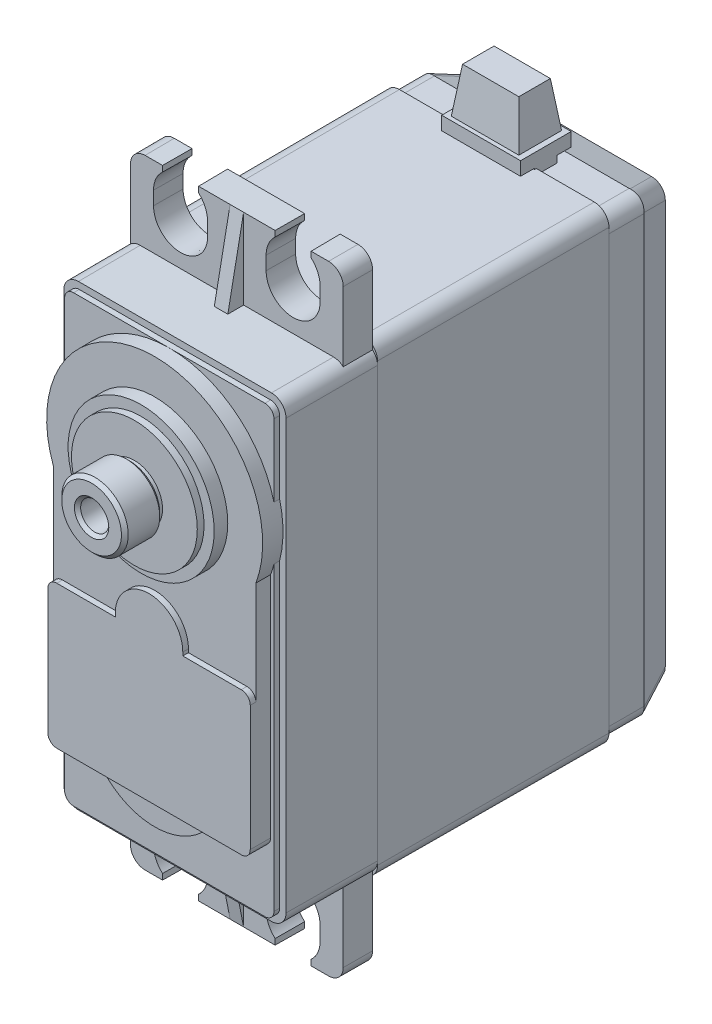
SolidWorks part; units mm, degrees
other "Camera1"
other "Camera3"
material "ABS"
ref_plane "front" through (0, 0, 0) normal (0, 0, 1) x (1, 0, 0)
ref_plane "上基準面" through (0, 0, 0) normal (0, 1, 0) x (1, 0, 0)
ref_plane "右基準面" through (0, 0, 0) normal (1, 0, 0) x (0, 0, -1)
sketch "Sketch1" plane through (0, 0, 0) normal (0, 0, 1) x (1, 0, 0)
  line L1 (-9.9, -20.7) -> (9.9, -20.7)
  line L2 (-9.9, -20.7) -> (-9.9, 20.7)
  line L3 (-9.9, 20.7) -> (9.9, 20.7)
  line L4 (9.9, -20.7) -> (9.9, 20.7)
  line L5 (-9.9, -20.7) -> (9.9, 20.7) construction
  line L6 (-9.9, 20.7) -> (9.9, -20.7) construction
  point P0 (0, 0)
  dimension "D1" = 19.8
  dimension "D2" = 41.4
extrude "Boss-Extrude1" add sketch "Sketch1" against normal blind 20.5 draft 0.15 draft outward yes
sketch "Sketch2" plane through (0, 0, -20.5) normal (0, 0, -1) x (-1, 0, 0)
  line L1 (-9.95, 20.25) -> (9.95, 20.25)
  line L2 (-9.95, 20.25) -> (-9.95, -20.25)
  line L3 (-9.95, -20.25) -> (9.95, -20.25)
  line L4 (9.95, 20.25) -> (9.95, -20.25)
  line L5 (-9.95, 20.25) -> (9.95, -20.25) construction
  line L6 (-9.95, -20.25) -> (9.95, 20.25) construction
  point P0 (0, 0)
  dimension "D1" = 19.9
  dimension "D2" = 40.5
extrude "Boss-Extrude2" add sketch "Sketch2" along normal blind 6.1
sketch "Sketch4" plane through (0, 0, 0) normal (0, 0, 1) x (1, 0, 0)
  line L0 (9.9, -20.7) -> (9.9, 20.7) construction
  line L1 (-9.9, 27.5) -> (9.9, 27.5)
  line L2 (-9.9, 27.5) -> (-9.9, -27.5)
  line L3 (-9.9, -27.5) -> (9.9, -27.5)
  line L4 (9.9, 27.5) -> (9.9, -27.5)
  line L5 (-9.9, 27.5) -> (9.9, -27.5) construction
  line L6 (-9.9, -27.5) -> (9.9, 27.5) construction
  point P0 (0, 0)
  dimension "D1" = 55
extrude "Boss-Extrude3" add sketch "Sketch4" along normal blind 2.6 draft 0.2
sketch "Sketch6" plane through (0, 0, 2.6) normal (0, 0, 1) x (1, 0, 0)
  line L0 (9.8909, -27.4909) -> (9.8909, 27.4909) construction
  line L1 (-9.8909, -20.35) -> (9.8909, -20.35)
  line L2 (-9.8909, -20.35) -> (-9.8909, 20.35)
  line L3 (-9.8909, 20.35) -> (9.8909, 20.35)
  line L4 (9.8909, -20.35) -> (9.8909, 20.35)
  line L5 (-9.8909, -20.35) -> (9.8909, 20.35) construction
  line L6 (-9.8909, 20.35) -> (9.8909, -20.35) construction
  point P0 (0, 0)
  dimension "D1" = 40.7
extrude "Boss-Extrude4" add sketch "Sketch6" along normal blind 6 draft 0.2
sketch "Sketch19" plane through (0, 0, 2.6) normal (0, 0, 1) x (1, 0, 0)
  line L0 (9.8909, 20.35) -> (-9.8909, 20.35) construction
  line L1 (-9.45, 20.35) -> (-11.45, 20.35)
  line L2 (-9.45, 20.35) -> (-9.45, 29.35)
  line L3 (-9.45, 29.35) -> (-11.45, 29.35)
  line L4 (-11.45, 20.35) -> (-11.45, 29.35)
  line L5 (0, 27.4909) -> (0, 34.543) construction
  line L6 (9.8909, 27.4909) -> (-9.8909, 27.4909) construction
  line L7 (11.45, 20.35) -> (11.45, 29.35)
  line L8 (9.45, 29.35) -> (11.45, 29.35)
  line L9 (9.45, 20.35) -> (9.45, 29.35)
  line L10 (9.45, 20.35) -> (11.45, 20.35)
  line L11 (0, 0) -> (31.6093, 0) construction
  line L12 (0, -27.4909) -> (0, -34.543) construction
  line L13 (9.45, -20.35) -> (11.45, -20.35)
  line L14 (9.45, -20.35) -> (9.45, -29.35)
  line L15 (9.45, -29.35) -> (11.45, -29.35)
  line L16 (11.45, -20.35) -> (11.45, -29.35)
  line L17 (-11.45, -20.35) -> (-11.45, -29.35)
  line L18 (-9.45, -29.35) -> (-11.45, -29.35)
  line L19 (-9.45, -20.35) -> (-9.45, -29.35)
  line L20 (-9.45, -20.35) -> (-11.45, -20.35)
  dimension "D1" = 18.9
  dimension "D2" = 2
  dimension "D3" = 9
extrude "Cut-Extrude4" cut sketch "Sketch19" against normal up to surface (2.6 mm away) draft 0.2 up to face at (2.475, 24.1, 0)
sketch "Sketch8" plane through (0, 0, 8.6) normal (0, 0, 1) x (1, 0, 0)
  line L1 (-9.3, 19.75) -> (9.3, 19.75)
  line L2 (-9.3, 19.75) -> (-9.3, -19.75)
  line L3 (-9.3, -19.75) -> (9.3, -19.75)
  line L4 (9.3, 19.75) -> (9.3, -19.75)
  line L5 (-9.3, 19.75) -> (9.3, -19.75) construction
  line L6 (-9.3, -19.75) -> (9.3, 19.75) construction
  point P0 (0, 0)
  dimension "D1" = 18.6
  dimension "D2" = 39.5
extrude "Cut-Extrude1" cut sketch "Sketch8" against normal blind 0.5 flip side to cut
sketch "Sketch9" plane through (0, 0, 8.1) normal (0, 0, 1) x (1, 0, 0)
  line L0 (9.3, 19.75) -> (-9.3, 19.75) construction
  line L2 (-9, 6.8093) -> (-9, -14.25)
  line L3 (-9, -14.25) -> (-4.7, -14.25)
  line L4 (9, 6.8093) -> (9, -14.25)
  line L5 (4.7, -14.25) -> (9, -14.25)
  arc A0 (9, 6.8093) -> (-9, 6.8093) centre (0, 10.15) ccw
  arc A1 (-4.7, -14.25) -> (4.7, -14.25) centre (0, -10.3295) ccw
  point P12 (0, -16.45)
  point P13 (0, 19.75)
  dimension "D1" = 19.2
  dimension "D2" = 18
  dimension "D3" = 9.4
  dimension "D4" = 36.2
  dimension "D5" = 34
extrude "Boss-Extrude5" add sketch "Sketch9" along normal blind 1.8
sketch "Sketch11" plane through (0, 0, 0) normal (1, 0, 0) x (0, 0, -1)
  line L0 (-7.9812, 10.15) -> (-20.2039, 10.15) construction
  line L1 (-8.6, 10.15) -> (-8.1, 10.15) construction
  line L2 (-9.9, 16.65) -> (-9.9, 10.15)
  line L3 (-9.9, 19.75) -> (-9.9, 6.8093) construction
  line L4 (-9.9, 10.15) -> (-11.7, 10.15)
  line L5 (-11.7, 10.15) -> (-11.7, 15.75)
  line L6 (-11.7, 15.75) -> (-11.1, 15.75)
  line L7 (-11.1, 15.75) -> (-11.1, 16.65)
  line L8 (-11.1, 16.65) -> (-9.9, 16.65)
  dimension "D1" = 1.8
  dimension "D2" = 11.2
  dimension "D3" = 13
  dimension "D4" = 1.2
revolve "Revolve1" add sketch "Sketch11" angle 360 about L0
sketch "Sketch13" plane through (0, 0, 0) normal (1, 0, 0) x (0, 0, -1)
  line L0 (-10.3101, 10.15) -> (-25.0492, 10.15) construction
  line L1 (-11.1, 10.15) -> (-9.9, 10.15) construction
  line L2 (-11.7, 12.65) -> (-11.7, 10.15)
  line L3 (-11.7, 15.75) -> (-11.7, 4.55) construction
  line L4 (-11.7, 10.15) -> (-15.5, 10.15)
  line L5 (-15.5, 10.15) -> (-15.5, 13.1)
  line L6 (-15.5, 13.1) -> (-12.1, 13.1)
  line L7 (-12.1, 13.1) -> (-12.1, 12.65)
  line L8 (-12.1, 12.65) -> (-11.7, 12.65)
  dimension "D1" = 5
  dimension "D2" = 5.9
  dimension "D3" = 3.8
  dimension "D4" = 3.4
revolve "Revolve2" add sketch "Sketch13" angle 360 about L0
chamfer "Chamfer1" distance 0.3 angle 45 2 edges at (0, 13.1, 15.5) (0, 13.1, 12.1)
draft "Draft1" type of draft neutral plane draft angle 0.2 faces to draft 14 face at (0, -19.75, 8.35) face at (-6.85, -14.25, 9.25) face at (0, -15.35, 9.25) face at (6.85, -14.25, 9.25) face at (9, -3.7203, 9.25) face at (9.3, -5.9906, 8.35) face at (9.3, 16.1406, 8.35) face at (-5.6, 10.15, 11.7) face at (-6.5, 10.15, 11.1) face at (-9.3, -5.9906, 8.35) face at (-9, -3.7203, 9.25) face at (0, 19.75, 8.4) face at (0, 11.1005, 8.6462) face at (-9.3, 16.1406, 8.35) neutral plane through (0, 0, 8.1) neutral plane normal (0, 0, 1) parameters "D1"=0.2
sketch "Sketch15" plane through (0, 0, 2.6) normal (0, 0, 1) x (1, 0, 0)
  line L0 (0, 27.4909) -> (0, 28.1897) construction
  line L1 (9.45, 27.4909) -> (-9.45, 27.4909) construction
  line L2 (2.6, 25.1909) -> (2.6, 23.9909)
  line L3 (9.4591, 27.5) -> (-9.4591, 27.5) construction
  line L4 (7.4, 25.1909) -> (7.4, 23.9909)
  line L5 (-6.6, 26.9798) -> (-6.6, 28)
  line L6 (3.4, 26.9798) -> (3.4, 28)
  line L7 (3.4, 28) -> (6.6, 28)
  line L8 (6.6, 26.9798) -> (6.6, 28)
  line L9 (-3.4, 28) -> (-6.6, 28)
  line L10 (-3.4, 26.9798) -> (-3.4, 28)
  line L11 (-7.4, 25.1909) -> (-7.4, 23.9909)
  line L12 (-2.6, 25.1909) -> (-2.6, 23.9909)
  line L13 (17.6765, 0) -> (38.8031, 0) construction
  line L14 (0, -27.4909) -> (0, -28.1897) construction
  line L15 (-2.6, -25.1909) -> (-2.6, -23.9909)
  line L16 (-7.4, -25.1909) -> (-7.4, -23.9909)
  line L17 (-3.4, -26.9798) -> (-3.4, -28)
  line L18 (-3.4, -28) -> (-6.6, -28)
  line L19 (6.6, -26.9798) -> (6.6, -28)
  line L20 (3.4, -28) -> (6.6, -28)
  line L21 (3.4, -26.9798) -> (3.4, -28)
  line L22 (-6.6, -26.9798) -> (-6.6, -28)
  line L23 (7.4, -25.1909) -> (7.4, -23.9909)
  line L24 (2.6, -25.1909) -> (2.6, -23.9909)
  arc A0 (7.4, 25.1909) -> (6.6, 26.9798) centre (5, 25.1909) ccw
  arc A1 (2.6, 23.9909) -> (7.4, 23.9909) centre (5, 23.9909) ccw
  arc A2 (3.4, 26.9798) -> (2.6, 25.1909) centre (5, 25.1909) ccw
  arc A3 (-3.4, 26.9798) -> (-2.6, 25.1909) centre (-5, 25.1909) cw
  arc A4 (-2.6, 23.9909) -> (-7.4, 23.9909) centre (-5, 23.9909) cw
  arc A5 (-7.4, 25.1909) -> (-6.6, 26.9798) centre (-5, 25.1909) cw
  arc A6 (-7.4, -25.1909) -> (-6.6, -26.9798) centre (-5, -25.1909) ccw
  arc A7 (-2.6, -23.9909) -> (-7.4, -23.9909) centre (-5, -23.9909) ccw
  arc A8 (-3.4, -26.9798) -> (-2.6, -25.1909) centre (-5, -25.1909) ccw
  arc A9 (3.4, -26.9798) -> (2.6, -25.1909) centre (5, -25.1909) cw
  arc A10 (2.6, -23.9909) -> (7.4, -23.9909) centre (5, -23.9909) cw
  arc A11 (7.4, -25.1909) -> (6.6, -26.9798) centre (5, -25.1909) cw
  point P1 (5, 21.5909)
  point P25 (-5, 21.5909)
  point P53 (-5, -21.5909)
  point P54 (5, -21.5909)
  dimension "D8" = 2.4
  dimension "D1" = 0.5
  dimension "D2" = 5.2
  dimension "D3" = 5.9
  dimension "D4" = 14.8
  dimension "D5" = 3.2
  dimension "D6" = 2.3
  dimension "D7" = 10
extrude "Cut-Extrude2" cut sketch "Sketch15" against normal through all draft 0.5
sketch "Sketch16" plane through (0, 0, 0) normal (1, 0, 0) x (0, 0, -1)
  line L0 (21.35, 27.1985) -> (21.35, 16.5944) construction
  line L1 (22.35, 20.8537) -> (23.6, 20.8537)
  line L2 (23.6, 20.8537) -> (23.6, 22.0537)
  line L3 (23.6, 22.0537) -> (23.25, 22.0537)
  line L4 (23.25, 22.0537) -> (22.75, 26.0537)
  line L5 (22.75, 26.0537) -> (19.95, 26.0537)
  line L6 (26.6, 20.25) -> (26.6, -20.25) construction
  line L7 (22.35, 20.8537) -> (22.35, 18.8537)
  line L8 (22.35, 18.8537) -> (20.35, 18.8537)
  line L9 (20.35, 20.8537) -> (20.35, 18.8537)
  line L10 (19.45, 22.0537) -> (19.95, 26.0537)
  line L11 (19.1, 22.0537) -> (19.45, 22.0537)
  line L12 (19.1, 20.8537) -> (19.1, 22.0537)
  line L13 (20.35, 20.8537) -> (19.1, 20.8537)
  point P12 (21.35, 18.8537)
  point P16 (21.35, 26.0537)
  dimension "D1" = 4.5
  dimension "D2" = 3
  dimension "D3" = 3.8
  dimension "D4" = 4
  dimension "D5" = 0.1
  dimension "D6" = 2.8
  dimension "D7" = 5.2
  dimension "D8" = 2
  dimension "D9" = 2
extrude "Boss-Extrude6" add sketch "Sketch16" along normal mid plane 7
sketch "Sketch17" plane through (0, 0, 0) normal (0, 0, 1) x (1, 0, 0)
  line L0 (3, 22.0537) -> (2.5, 26.0537)
  line L1 (3.5, 22.0537) -> (-3.5, 22.0537) construction
  line L2 (3.5, 26.0537) -> (-3.5, 26.0537) construction
  line L3 (2.5, 26.0537) -> (-2.5, 26.0537)
  line L4 (-2.5, 26.0537) -> (-3, 22.0537)
  line L5 (-3, 22.0537) -> (-3.5, 22.0537)
  line L6 (-3.5, 22.0537) -> (-3.5, 28.0537)
  line L7 (-3.5, 28.0537) -> (3.5, 28.0537)
  line L8 (3.5, 28.0537) -> (3.5, 22.0537)
  line L9 (3.5, 22.0537) -> (3, 22.0537)
  line L10 (-3.5, 22.0537) -> (-3.5, 26.0537) construction
  dimension "D1" = 2
  dimension "D2" = 6
  dimension "D3" = 5
extrude "Cut-Extrude3" cut sketch "Sketch17" against normal through all
sketch "Sketch18" plane through (0, 0, 0) normal (1, 0, 0) x (0, 0, -1)
  line L0 (-2.6, 27.4909) -> (-2.6, 20.3451)
  line L1 (-2.6, 20.3451) -> (-4, 20.3451)
  line L2 (-4, 20.3451) -> (-2.6, 27.4909)
  line L3 (-8.1, 20.3308) -> (0, 20.3591) construction
  line L4 (0, -55) -> (0, 27.5) construction
  line L5 (-2.6, 27.4909) -> (0, 27.5) construction
  line L6 (-2.6, 27.4909) -> (-2.6, 20.35) construction
  dimension "D1" = 4
extrude "Boss-Extrude7" add sketch "Sketch18" along normal mid plane 1.2
mirror "Mirror1" about plane through (0, 0, 0) normal (0, 1, 0) of "Boss-Extrude7"
sketch "Sketch20" plane through (0, 0, 9.9) normal (0, 0, 1) x (1, 0, 0)
  line L0 (-8.9937, 6.8105) -> (-8.9937, -14.2437) construction
  line L1 (8.9937, -14.2437) -> (-8.9937, -14.2437)
  line L2 (8.9937, -14.2437) -> (8.9937, -1.5437)
  line L3 (8.9937, -1.5437) -> (3, -1.5437)
  line L4 (-8.9937, -14.2437) -> (-8.9937, -1.5437)
  line L5 (-3, -1.5437) -> (-8.9937, -1.5437)
  line L6 (-3, -1.2437) -> (-3, -1.5437)
  line L7 (3, -1.2437) -> (3, -1.5437)
  arc A0 (-3, -1.2437) -> (3, -1.2437) centre (0, -1.2437) cw
  point P10 (0, 1.7563)
  dimension "D4" = 3
  dimension "D1" = 0.3
  dimension "D2" = 16
  dimension "D3" = 12.7
extrude "Boss-Extrude8" add sketch "Sketch20" along normal blind 0.5 draft 0.2
chamfer "Chamfer2" distance 3 angle 20 4 edges at (0, -20.25, -26.6) (-9.95, 0, -26.6) (0, 20.25, -26.6) (9.95, 0, -26.6)
fillet "Fillet1" radius 1.3 28 edges at (9.4545, -20.3545, 1.3) (9.6795, -20.3591, 0) (9.4545, -27.4955, 1.3) (-9.6795, -20.3591, 0) (-9.4545, -27.4955, 1.3) (-9.4545, -20.3545, 1.3) (-9.95, -20.25, -22.05) (9.95, -20.25, -22.05) (-9.95, 20.25, -22.05) (9.95, 20.25, -22.05) (9.404, 19.704, -25.1) (-9.404, 19.704, -25.1) (9.404, -19.704, -25.1) (-9.404, -19.704, -25.1) (-9.6795, 20.3591, 0) (-9.4545, 20.3545, 1.3) (-9.4545, 27.4955, 1.3) (9.6795, 20.3591, 0) (9.4545, 27.4955, 1.3) (9.4545, 20.3545, 1.3)
fillet "Fillet2" radius 1.3 4 edges
fillet "Fillet3" radius 0.8 8 edges at (-8.9928, -1.5446, 10.15) (8.9928, -1.5446, 10.15) (8.9951, -14.2451, 9.5) (-8.9951, -14.2451, 9.5) (9.2991, -19.7491, 8.35) (-9.2991, -19.7491, 8.35) (9.2991, 19.7491, 8.35) (-9.2991, 19.7491, 8.35)
hole_wizard "M3x0.5 Tapped Hole1" positions "Sketch22" profile "Sketch21" tap size "M3x0.5" standard "JIS"
sketch "Sketch22" plane through (0, 0, 15.5) normal (0, 0, 1) x (1, 0, 0)
  point P0 (0, 10.15)
sketch "Sketch21" plane through (0, 10.15, 15.5) normal (1, 0, 0) x (0, -1, 0)
  line L0 (0, 0) -> (0, 7.2511)
  line L1 (0, 7.2511) -> (1.25, 6.5)
  line L2 (1.25, 6.5) -> (1.25, 0.275)
  line L3 (1.25, 0.275) -> (1.525, 0)
  line L5 (1.525, 0) -> (0, 0)
  line L6 (-1.25, 0.275) -> (-1.525, 0) construction
  line L10 (0, 7.2511) -> (-1.25, 6.5) construction
  line L11 (0, -6.35) -> (0, 107.95) construction
  dimension "Tap Drill Dia." = 2.5
  dimension "Tap Drill Depth" = 6.5
  dimension "Near C'Sink Dia." = 3.05
  dimension "Near C'Sink Angle" = 90
  dimension "Drill Angle" = 118
cosmetic thread "Hole Thread1" parameters "D1"=5, "D2"=3
